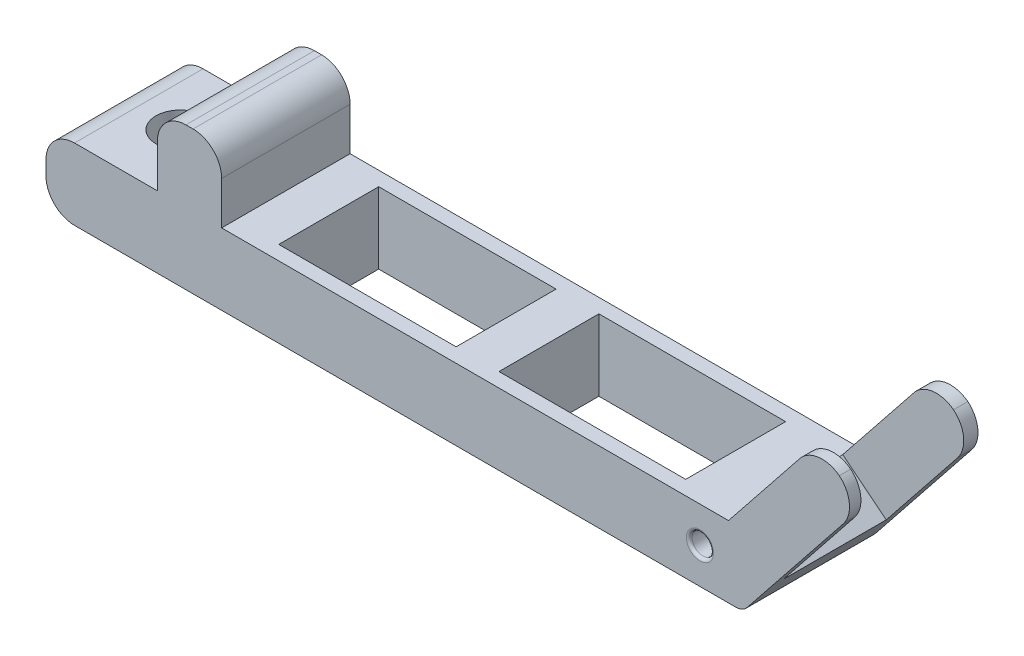
SolidWorks part; units mm, degrees
ref_plane "Front Plane" through (0, 0, 0) normal (0, 0, 1) x (1, 0, 0)
ref_plane "Top Plane" through (0, 0, 0) normal (0, 1, 0) x (1, 0, 0)
ref_plane "Right Plane" through (0, 0, 0) normal (1, 0, 0) x (0, 0, -1)
sketch "Szkic1" plane through (0, 0, 0) normal (0, 0, 1) x (1, 0, 0)
  line L6 (-27646.5587, -28.9023) -> (-27646.5587, -33.9023)
  line L7 (-27646.5587, -33.9023) -> (-27597.7587, -33.9023)
  line L8 (-27597.7587, -33.9023) -> (-27589.4735, -23.5176)
  line L9 (-27589.4735, -23.5176) -> (-27592.5221, -21.0854)
  line L10 (-27592.5221, -21.0854) -> (-27598.7587, -28.9023)
  line L11 (-27598.7587, -28.9023) -> (-27634.2587, -28.9023)
  line L12 (-27638.7587, -28.9023) -> (-27638.7587, -23.9023)
  line L13 (-27638.7587, -23.9023) -> (-27634.2587, -23.9023)
  line L14 (-27634.2587, -23.9023) -> (-27634.2587, -28.9023)
  line L15 (-27638.7587, -28.9023) -> (-27646.5587, -28.9023)
  line L16 (-27600.7587, -28.9023) -> (-27600.7587, -33.9023) construction
  circle A0 centre (-27600.7587, -31.4023) radius 0.75
  point P12 (-27600.7587, -31.4023)
  dimension "D9" = 1.5
  dimension "D1" = 3.9
  dimension "D2" = 47.8
  dimension "D3" = 10
  dimension "D4" = 5
  dimension "D5" = 48.8
  dimension "D6" = 4.5
  dimension "D7" = 5
  dimension "D8" = 7.8
  dimension "D10" = 2
extrude "Dodanie-wyciągnięcie1" add sketch "Szkic1" along normal blind 9
fillet "Zaokrąglenie1" radius 2 4 edges at (-27646.5587, -33.9023, 4.5) (-27634.2587, -23.9023, 4.5) (-27638.7587, -23.9023, 4.5) (-27646.5587, -28.9023, 4.5)
fillet "Zaokrąglenie3" radius 1 1 edges at (-27597.7587, -33.9023, 4.5)
ref_plane "Płaszczyzna1" through (0, -28.9023, 0) normal (0, 1, 0) x (1, 0, 0)
sketch "Szkic2" plane through (0, -28.9023, 0) normal (0, 1, 0) x (1, 0, 0)
  line L0 (-27641.6587, 0) -> (-27641.6587, -9) construction
  line L1 (-27638.7587, 0) -> (-27644.5587, 0) construction
  line L2 (-27638.7587, -9) -> (-27644.5587, -9) construction
  circle A0 centre (-27641.6587, -4.5) radius 1.7
  point P6 (-27641.6587, -4.5)
  dimension "D1" = 3.4
extrude "Wytnij-wyciągnięcie1" cut sketch "Szkic2" against normal through all
ref_plane "Płaszczyzna2" through (0, -28.9023, 0) normal (0, 1, 0) x (1, 0, 0)
sketch "Szkic3" plane through (0, -28.9023, 0) normal (0, 1, 0) x (1, 0, 0)
  line L0 (-27634.2587, -4.5) -> (-27598.7587, -4.5) construction
  line L1 (-27634.2587, -9) -> (-27634.2587, 0) construction
  line L2 (-27598.7587, -9) -> (-27598.7587, 0) construction
  line L3 (-27598.7587, -9) -> (-27634.2587, -9) construction
  line L4 (-27602.7587, -8) -> (-27615.8361, -8)
  line L5 (-27602.7587, -8) -> (-27602.7587, -1)
  line L6 (-27602.7587, -1) -> (-27615.8361, -1)
  line L7 (-27615.8361, -8) -> (-27615.8361, -1)
  line L8 (-27602.7587, -8) -> (-27615.8361, -1) construction
  line L9 (-27602.7587, -1) -> (-27615.8361, -8) construction
  line L10 (-27631.2587, -1) -> (-27618.8361, -1)
  line L11 (-27631.2587, -1) -> (-27631.2587, -8)
  line L12 (-27631.2587, -8) -> (-27618.8361, -8)
  line L13 (-27618.8361, -1) -> (-27618.8361, -8)
  line L14 (-27631.2587, -1) -> (-27618.8361, -8) construction
  line L15 (-27631.2587, -8) -> (-27618.8361, -1) construction
  point P6 (-27609.2974, -4.5)
  point P11 (-27625.0474, -4.5)
  dimension "D1" = 3
  dimension "D2" = 4
  dimension "D3" = 3
  dimension "D4" = 1
extrude "Wytnij-wyciągnięcie2" cut sketch "Szkic3" against normal through all
ref_plane "Płaszczyzna3" through (-16850.0467, 13443.5022, 0) normal (-0.7817, 0.6237, 0) x (0, 0, 1)
sketch "Szkic4" plane through (-16850.0467, 13443.5022, 0) normal (-0.7817, 0.6237, 0) x (0, 0, 1)
  line L0 (9, -17234.8628) -> (0, -17234.8628) construction
  line L1 (1, -17234.8628) -> (8.2, -17234.8628)
  line L2 (1, -17234.8628) -> (1, -17222.0924)
  line L3 (1, -17222.0924) -> (8.2, -17222.0924)
  line L4 (8.2, -17234.8628) -> (8.2, -17222.0924)
  line L5 (0, -17224.8628) -> (0, -17234.8628) construction
  dimension "D1" = 7.2
  dimension "D2" = 1
extrude "Wytnij-wyciągnięcie3" cut sketch "Szkic4" against normal through all
ref_plane "Płaszczyzna4" through (0, 0, 1) normal (0, 0, 1) x (1, 0, 0)
sketch "Szkic5" plane through (0, 0, 1) normal (0, 0, 1) x (1, 0, 0)
  line L0 (-27590.9978, -22.3015) -> (-27597.2344, -30.1185) construction
  line L1 (-27592.5221, -21.0854) -> (-27589.4735, -23.5176) construction
  line L2 (-27595.7101, -31.3346) -> (-27598.7587, -28.9023) construction
  circle A0 centre (-27592.3166, -23.9544) radius 0.5
  dimension "D1" = 1
extrude "Dodanie-wyciągnięcie2" [suppressed] add sketch "Szkic5" along normal up to next
fillet "Zaokrąglenie4" radius 2 4 edges at (-27589.4735, -23.5176, 0.5) (-27592.5221, -21.0854, 0.5) (-27589.4735, -23.5176, 8.6) (-27592.5221, -21.0854, 8.6)
fillet "Zaokrąglenie5" radius 1 1 edges at (-27643.3587, -33.9023, 4.5)
ref_axis "Oś1" through (-27641.6587, -32.9023, 4.5) along (0, 1, 0)
ref_point "Punkt1"
ref_point "Punkt2"
fillet "Zaokrąglenie7" radius 0.2 2 edges at (-27600.0087, -31.4023, 9) (-27600.0087, -31.4023, 0)
ref_plane "Płaszczyzna Dolnia" through (0, -33.9023, 0) normal (0, -1, 0) x (-1, 0, 0)
